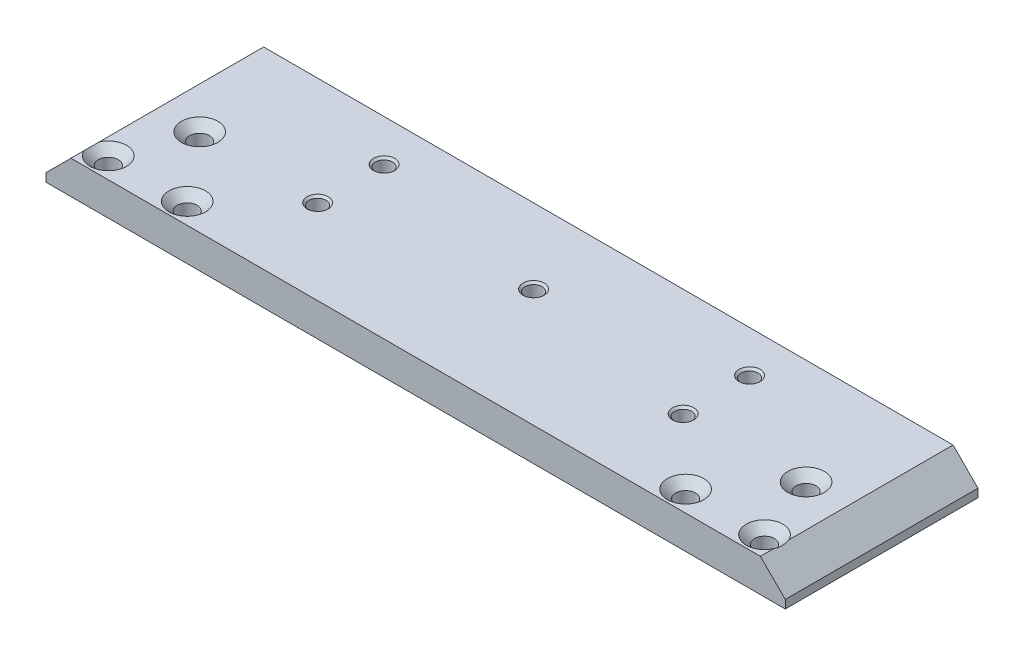
SolidWorks part; units mm, degrees
material "6061-T6 (SS)"
ref_plane "Front Plane" through (0, 0, 0) normal (0, 0, 1) x (1, 0, 0)
ref_plane "Top Plane" through (0, 0, 0) normal (0, 1, 0) x (1, 0, 0)
ref_plane "Right Plane" through (0, 0, 0) normal (1, 0, 0) x (0, 0, -1)
sketch "Sketch1" plane through (0, 0, 0) normal (0, 1, 0) x (1, 0, 0)
  line L1 (44.5, -11.6) -> (-44.5, -11.6)
  line L2 (44.5, -11.6) -> (44.5, 11.6)
  line L3 (44.5, 11.6) -> (-44.5, 11.6)
  line L4 (-44.5, -11.6) -> (-44.5, 11.6)
  line L5 (44.5, -11.6) -> (-44.5, 11.6) construction
  line L6 (44.5, 11.6) -> (-44.5, -11.6) construction
  point P0 (0, 0)
  dimension "D1" = 89
  dimension "D2" = 23.2
extrude "Boss-Extrude1" add sketch "Sketch1" along normal blind 4
hole_wizard "M2.5x0.45 Tapped Hole2" positions "Sketch4" profile "Sketch5" tap size "M2.5x0.45" standard "ANSI Metric" end condition through all
sketch "Sketch4" plane through (0, 4, 0) normal (0, 1, 0) x (1, 0, 0)
  line L0 (44.5, 11.6) -> (-44.5, 11.6) construction
  point P0 (-22, 6.6)
  point P2 (-22, -1.4)
  point P4 (22, -1.4)
  point P6 (22, 6.6)
  point P8 (0, 2.6)
  dimension "D1" = 8
  dimension "D2" = 8
  dimension "D3" = 44
  dimension "D4" = 22
  dimension "D5" = 9
  dimension "D6" = 4
  dimension "D7" = 4
cosmetic thread "Hole Thread6" parameters "D2"=2.5
cosmetic thread "Hole Thread7" parameters "D2"=2.5
cosmetic thread "Hole Thread8" parameters "D2"=2.5
cosmetic thread "Hole Thread9" parameters "D2"=2.5
cosmetic thread "Hole Thread10" parameters "D2"=2.5
sketch "Sketch5" plane through (-22, 4, -6.6) normal (1, 0, 0) x (0, 0, 1)
  line L0 (0, 0) -> (0, 4)
  line L1 (0, 4) -> (1.025, 4)
  line L2 (1.025, 4) -> (1.025, 0.25)
  line L3 (1.025, 0.25) -> (1.275, 0)
  line L5 (1.275, 0) -> (0, 0)
  line L6 (-1.025, 0.25) -> (-1.275, 0) construction
  line L11 (0, -6.35) -> (0, 107.95) construction
  dimension "Thru Tap Drill Dia." = 2.05
  dimension "Thru Tap Drill Depth" = 4
  dimension "Near C'Sink Dia." = 2.55
  dimension "Near C'Sink Angle" = 90
hole_wizard "CSK for M2 Flat Head Machine Screw1" positions "Sketch6" profile "Sketch7" countersink size "M2" standard "ANSI Metric"
sketch "Sketch6" plane through (0, 4, 0) normal (0, 1, 0) x (1, 0, 0)
  line L0 (-44.5, -11.6) -> (44.5, -11.6) construction
  circle A0 centre (0, 2.6) radius 1.025 construction
  point P0 (-36.5, -1.1)
  point P2 (-39.5, -9.1)
  point P4 (-30, -9.1)
  point P6 (30, -9.1)
  point P8 (39.5, -9.1)
  point P10 (36.5, -1.1)
  dimension "D5" = 39.5
  dimension "D1" = 39.5
  dimension "D2" = 3
  dimension "D3" = 8
  dimension "D4" = 9.5
  dimension "D6" = 3
  dimension "D7" = 9.5
  dimension "D8" = 8
  dimension "D9" = 2.5
  dimension "D10" = 2.5
sketch "Sketch7" plane through (-36.5, 4, 1.1) normal (1, 0, 0) x (0, 0, 1)
  line L0 (0, 0) -> (0, 7.171)
  line L1 (0, 7.171) -> (1.2, 6.45)
  line L2 (1.2, 6.45) -> (1.2, 1)
  line L3 (1.2, 1) -> (2.2, 0)
  line L5 (2.2, 0) -> (0, 0)
  line L6 (-1.2, 1) -> (-2.2, 0) construction
  line L10 (0, 7.171) -> (-1.2, 6.45) construction
  line L11 (0, -6.35) -> (0, 107.95) construction
  dimension "Hole Dia." = 2.4
  dimension "Hole Depth" = 6.45
  dimension "Near C'Sink Dia." = 4.4
  dimension "Near C'Sink Angle" = 90
  dimension "Drill Angle" = 118
sketch "Sketch8" plane through (0, 0, 11.6) normal (0, 0, 1) x (1, 0, 0)
  line L9 (41.5, 4) -> (44.5, 4)
  line L10 (-44.5, 4) -> (44.5, 4) construction
  line L11 (44.5, 4) -> (44.5, 1)
  line L12 (44.5, 4) -> (44.5, 0) construction
  line L13 (44.5, 1) -> (41.5, 4)
  line L14 (-44.5, 4) -> (-44.5, 1)
  line L15 (-44.5, 4) -> (-44.5, 0) construction
  line L16 (-44.5, 1) -> (-41.5, 4)
  line L17 (-41.5, 4) -> (-44.5, 4)
  dimension "D1" = 3
  dimension "D2" = 1
  dimension "D3" = 1
  dimension "D4" = 3
extrude "Cut-Extrude1" cut sketch "Sketch8" against normal up to surface (23.2 mm away) up to face at (0, 2, -11.6)
